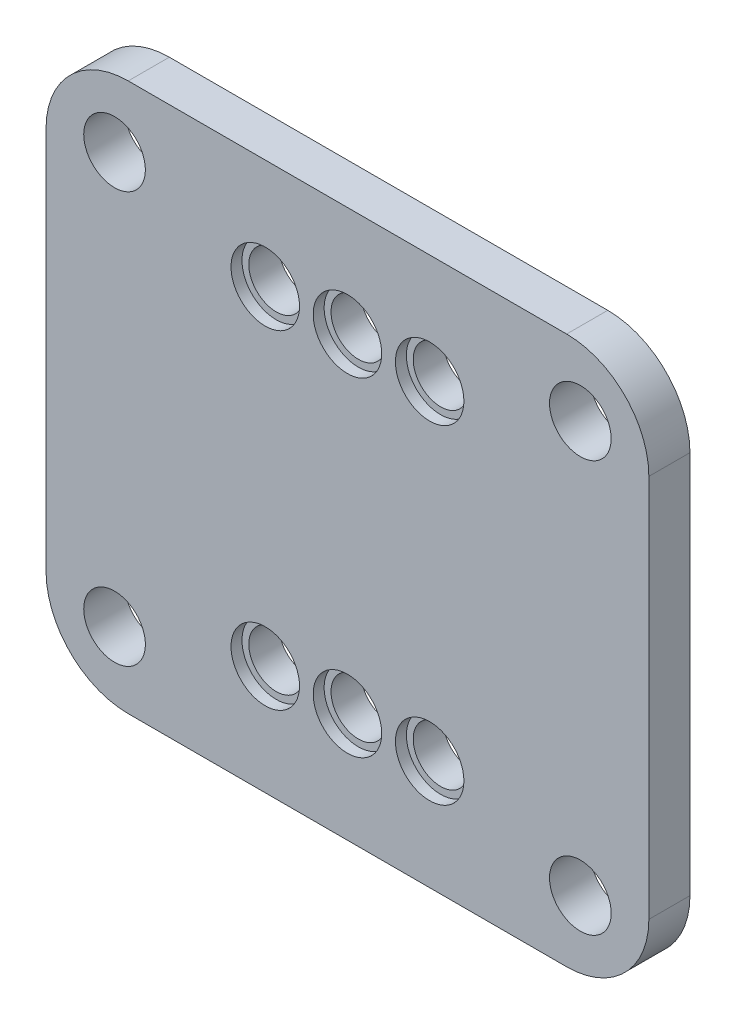
SolidWorks part; units mm, degrees
ref_plane "Plan de face" through (0, 0, 0) normal (0, 0, 1) x (1, 0, 0)
ref_plane "Plan de dessus" through (0, 0, 0) normal (0, 1, 0) x (1, 0, 0)
ref_plane "Plan de droite" through (0, 0, 0) normal (1, 0, 0) x (0, 0, -1)
sketch "Esquisse2" plane through (0, 0, 0) normal (0, 0, 1) x (1, 0, 0)
  line L1 (0, 0) -> (44, 0)
  line L2 (0, 0) -> (0, 40)
  line L3 (0, 40) -> (44, 40)
  line L4 (44, 0) -> (44, 40)
  dimension "D1" = 44
  dimension "D2" = 40
extrude "Boss.-Extru.1" add sketch "Esquisse2" along normal blind 3
sketch "Esquisse3" plane through (0, 0, 3) normal (0, 0, 1) x (1, 0, 0)
  line L0 (22, 0) -> (22, 40) construction
  line L1 (0, 0) -> (44, 0) construction
  line L2 (44, 40) -> (0, 40) construction
  line L3 (0, 20) -> (44, 20) construction
  line L4 (0, 40) -> (0, 0) construction
  line L5 (44, 0) -> (44, 40) construction
  line L6 (16, 32) -> (22, 32) construction
  line L7 (16, 8) -> (22, 8) construction
  circle A0 centre (22, 32) radius 2
  circle A1 centre (16, 32) radius 2
  circle A2 centre (28, 32) radius 2
  circle A3 centre (28, 8) radius 2
  circle A4 centre (16, 8) radius 2
  circle A5 centre (22, 8) radius 2
  circle A6 centre (5, 35) radius 2.25
  circle A7 centre (5, 5) radius 2.25
  circle A8 centre (39, 5) radius 2.25
  circle A9 centre (39, 35) radius 2.25
  dimension "D1" = 4
  dimension "D2" = 24
  dimension "D3" = 6
  dimension "D4" = 4.5
  dimension "D5" = 30
  dimension "D6" = 34
extrude "Enlèv. mat.-Extru.1" cut sketch "Esquisse3" against normal through all both and the other way through all
fillet "Congé1" radius 6 4 edges at (0, 40, 1.5) (0, 0, 1.5) (44, 0, 1.5) (44, 40, 1.5)
sketch "Esquisse4" plane through (0, 0, 3) normal (0, 0, 1) x (1, 0, 0)
  circle A0 centre (16, 8) radius 2.5
  circle A1 centre (22, 8) radius 2.5
  circle A2 centre (28, 8) radius 2.5
  circle A3 centre (28, 32) radius 2.5
  circle A4 centre (22, 32) radius 2.5
  circle A5 centre (16, 32) radius 2.5
  dimension "D1" = 5
extrude "Enlèv. mat.-Extru.2" cut sketch "Esquisse4" against normal blind 0.8
